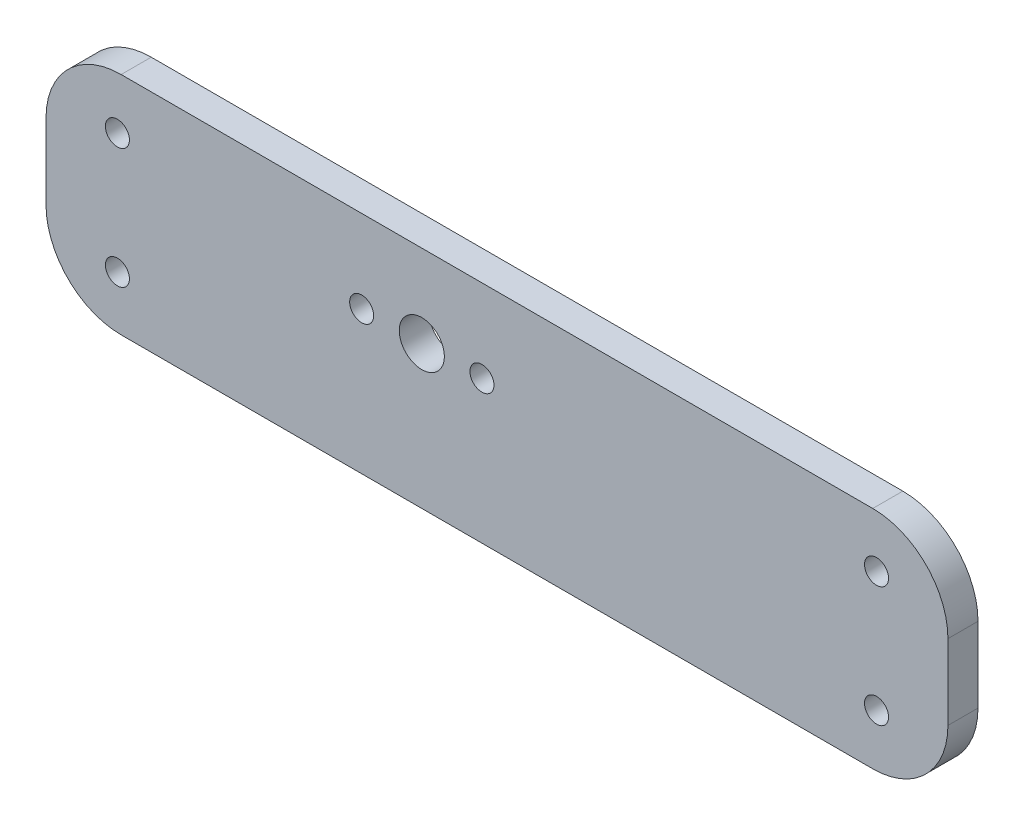
SolidWorks part; units mm, degrees
ref_plane "Plano frontal" through (0, 0, 0) normal (0, 0, 1) x (1, 0, 0)
ref_plane "Plano superior" through (0, 0, 0) normal (0, 1, 0) x (1, 0, 0)
ref_plane "Plano direito" through (0, 0, 0) normal (1, 0, 0) x (0, 0, -1)
sketch "Esboço1" plane through (0, 0, 0) normal (0, 0, 1) x (1, 0, 0)
  line L0 (-18, 4) -> (-2, 4) construction
  line L1 (-60, -15) -> (60, -15)
  line L2 (-60, -15) -> (-60, 15)
  line L3 (-60, 15) -> (60, 15)
  line L4 (60, -15) -> (60, 15)
  line L5 (0, 15) -> (0, -15) construction
  line L6 (-60, 0) -> (60, 0) construction
  line L7 (41, 15) -> (41, -15) construction
  line L8 (-41, 15) -> (-41, -15) construction
  line L9 (-41, 5.3275) -> (-60, 5.3275) construction
  circle A0 centre (-10, 4) radius 3
  circle A1 centre (-2, 4) radius 1.6
  circle A2 centre (-18, 4) radius 1.6
  circle A4 centre (-50.5, 8) radius 1.6
  circle A5 centre (-50.5, -8) radius 1.6
  circle A6 centre (50.5, -8) radius 1.6
  circle A7 centre (50.5, 8) radius 1.6
  point P0 (0, 0)
  point P21 (-50.5, 5.3275)
  dimension "D1" = 3.2
  dimension "D2" = 6
  dimension "D4" = 31
  dimension "D9" = 16
  dimension "D3" = 16
  dimension "D5" = 11
  dimension "D6" = 19
  dimension "D7" = 51
  dimension "D8" = 30
extrude "Ressalto-extrusão1" add sketch "Esboço1" along normal blind 4
fillet "Filete1" radius 10 4 edges at (-60, 15, 2) (-60, -15, 2) (60, -15, 2) (60, 15, 2)
